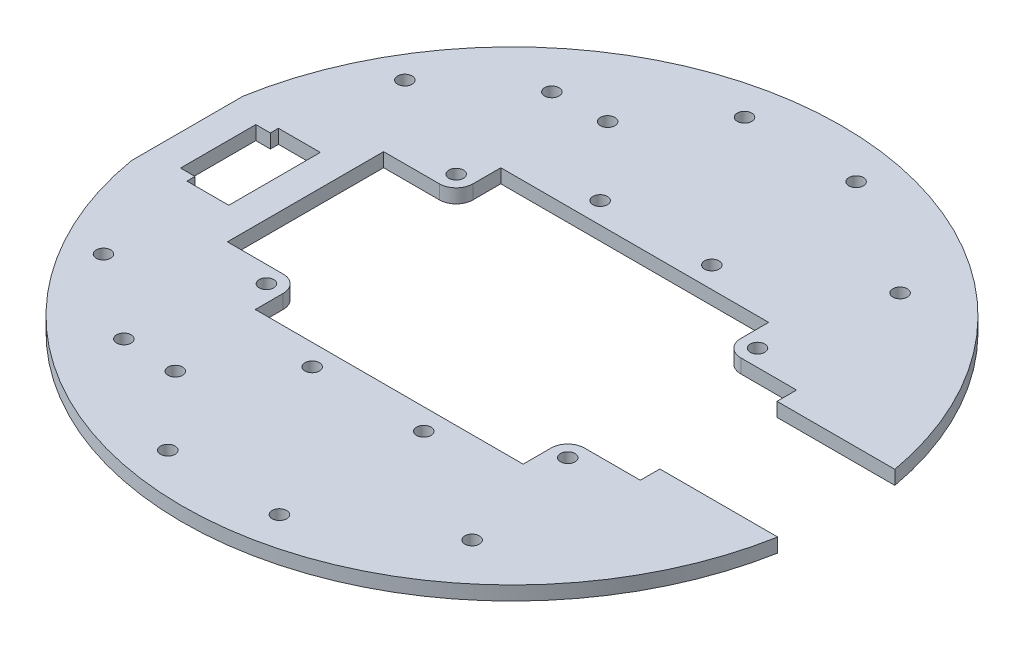
SolidWorks part; units mm, degrees
material "Acrylic (Medium-high impact)"
ref_plane "Front Plane" through (0, 0, 0) normal (0, 0, 1) x (1, 0, 0)
ref_plane "Top Plane" through (0, 0, 0) normal (0, 1, 0) x (1, 0, 0)
ref_plane "Right Plane" through (0, 0, 0) normal (1, 0, 0) x (0, 0, -1)
sketch "Sketch1" plane through (0, 0, 0) normal (0, 1, 0) x (1, 0, 0)
  line L0 (-73.9169, 12.7) -> (-73.9169, -12.7)
  line L1 (-73.9169, 12.7) -> (-73.9169, -12.7) construction
  line L2 (-34.29, 21.59) -> (34.29, 21.59) construction
  line L3 (34.29, 21.59) -> (34.29, -21.59) construction
  line L4 (34.29, -21.59) -> (-34.29, -21.59) construction
  line L5 (-34.29, -21.59) -> (-34.29, 21.59) construction
  line L6 (0, 21.59) -> (0, 75) construction
  line L7 (34.29, 0) -> (75, 0) construction
  line L8 (0, -25.4) -> (0, -21.59) construction
  line L9 (-34.29, 0) -> (-38.1, 0) construction
  line L10 (-30.48, 27.94) -> (30.48, 27.94)
  line L11 (-30.48, 27.94) -> (-30.48, 21.59)
  line L12 (0, 21.59) -> (0, 27.94) construction
  line L13 (30.48, 27.94) -> (30.48, 21.59)
  line L14 (34.29, 17.78) -> (46.99, 17.78)
  line L16 (34.29, -17.78) -> (46.99, -17.78)
  line L17 (46.99, 17.78) -> (46.99, -17.78)
  line L19 (30.48, -21.59) -> (30.48, -27.94)
  line L20 (30.48, -27.94) -> (-30.48, -27.94)
  line L21 (-30.48, -21.59) -> (-30.48, -27.94)
  line L22 (-46.99, -17.78) -> (-34.29, -17.78)
  line L23 (-46.99, -17.78) -> (-46.99, 17.78)
  line L24 (-46.99, 17.78) -> (-34.29, 17.78)
  line L28 (-24.25, -35.9484) -> (24.25, -35.9484) construction
  line L29 (24.25, -35.9484) -> (24.25, -62.4484) construction
  line L30 (-12.7, -35.9484) -> (-12.7, -32.7734) construction
  line L31 (24.25, -62.4484) -> (-24.25, -62.4484) construction
  line L32 (-24.25, -62.4484) -> (-24.25, -35.9484) construction
  line L33 (-24.25, -62.4484) -> (-27.1489, -69.9138) construction
  line L34 (24.25, -62.4484) -> (27.1489, -69.9138) construction
  line L35 (-24.25, -35.9484) -> (-24.25, -27.94) construction
  line L36 (0, -35.9484) -> (0, -62.4484) construction
  line L37 (-54.04, 0) -> (-46.99, 0) construction
  line L38 (-27.425, -49.1984) -> (-24.25, -49.1984) construction
  line L39 (-12.7, -65.6234) -> (-12.7, -62.4484) construction
  line L40 (-66.867, 8.5725) -> (-63.565, 8.5725)
  line L41 (-66.867, 8.5725) -> (-66.867, -8.5725)
  line L42 (-66.867, -8.5725) -> (-63.565, -8.5725)
  line L43 (-54.04, 8.5725) -> (-54.04, -8.5725)
  line L44 (-63.565, 8.5725) -> (-63.565, 10.414)
  line L45 (-63.565, 10.414) -> (-54.04, 10.414)
  line L46 (-54.04, 10.414) -> (-54.04, 8.5725)
  line L47 (-63.565, -8.5725) -> (-63.565, -10.414)
  line L48 (-63.565, -10.414) -> (-54.04, -10.414)
  line L49 (-54.04, -10.414) -> (-54.04, -8.5725)
  line L50 (-66.867, 0) -> (-73.9169, 0) construction
  line L51 (55.1757, 50.8) -> (55.1757, -50.8) construction
  arc A0 (-73.9169, -12.7) -> (-73.9169, 12.7) centre (0, 0) ccw
  arc A1 (55.356, -50.6035) -> (55.356, 50.6035) centre (0, 0) ccw construction
  circle A2 centre (-34.29, 21.59) radius 1.651
  circle A3 centre (34.29, 21.59) radius 1.651
  circle A4 centre (-34.29, -21.59) radius 1.651
  circle A5 centre (34.29, -21.59) radius 1.651
  circle A6 centre (-39.6269, 48.6985) radius 1.651 construction
  circle A7 centre (39.6269, -48.6985) radius 1.651
  circle A8 centre (-39.6269, -48.6985) radius 1.651
  circle A9 centre (-58.6769, -34.29) radius 1.651
  circle A10 centre (-58.6769, 34.29) radius 1.651
  circle A11 centre (-39.6269, 48.6985) radius 1.651
  circle A12 centre (39.6269, 48.6985) radius 1.651
  circle A13 centre (39.6269, -48.6985) radius 1.651 construction
  circle A14 centre (12.7, -65.6234) radius 1.651
  circle A15 centre (12.7, -32.7734) radius 1.651
  circle A16 centre (12.7, 32.7734) radius 1.651
  circle A17 centre (12.7, 65.6234) radius 1.651
  arc A18 (-34.29, 17.78) -> (-30.48, 21.59) centre (-34.29, 21.59) ccw
  arc A19 (-34.29, -17.78) -> (-30.48, -21.59) centre (-34.29, -21.59) cw
  arc A20 (30.48, 21.59) -> (34.29, 17.78) centre (34.29, 21.59) ccw
  arc A21 (30.48, -21.59) -> (34.29, -17.78) centre (34.29, -21.59) cw
  circle A22 centre (-27.425, -49.1984) radius 1.651
  circle A23 centre (-12.7, -32.7734) radius 1.651
  circle A24 centre (-12.7, -65.6234) radius 1.651
  circle A25 centre (-12.7, 65.6234) radius 1.651
  circle A26 centre (-27.425, 49.1984) radius 1.651
  circle A27 centre (-12.7, 32.7734) radius 1.651
  dimension "D11" = 3.302
  dimension "D1" = 68.58
  dimension "D2" = 43.18
  dimension "D3" = 3.81
  dimension "D4" = 12.7
  dimension "D5" = 60.96
  dimension "D6" = 35.56
  dimension "D7" = 48.5
  dimension "D8" = 26.5
  dimension "D9" = 12.7
  dimension "D10" = 3.175
  dimension "D12" = 17.145
  dimension "D13" = 6.35
  dimension "D14" = 101.6
  dimension "D15" = 3.302
  dimension "D16" = 20.828
  dimension "D17" = 9.525
extrude "Boss-Extrude1" add sketch "Sketch1" along normal blind 3.175
sketch "Sketch2" plane through (0, 3.175, 0) normal (0, 1, 0) x (1, 0, 0)
  line L0 (46.99, -17.78) -> (46.99, 17.78) construction
  line L1 (46.99, 13.335) -> (73.805, 13.335)
  line L2 (50.3421, 13.335) -> (43.9921, 13.335) construction
  line L3 (46.99, -13.335) -> (73.805, -13.335)
  line L5 (43.9921, -13.335) -> (50.3421, -13.335) construction
  line L6 (46.99, 13.335) -> (46.99, -13.335)
  arc A0 (-73.9169, -12.7) -> (-73.9169, 12.7) centre (0, 0) ccw construction
  arc A1 (73.805, 13.335) -> (73.805, -13.335) centre (0, 0) cw
extrude "Cut-Extrude1" cut sketch "Sketch2" against normal up to surface (3.175 mm away) up to face at (-27.425, 0, -50.8494)
